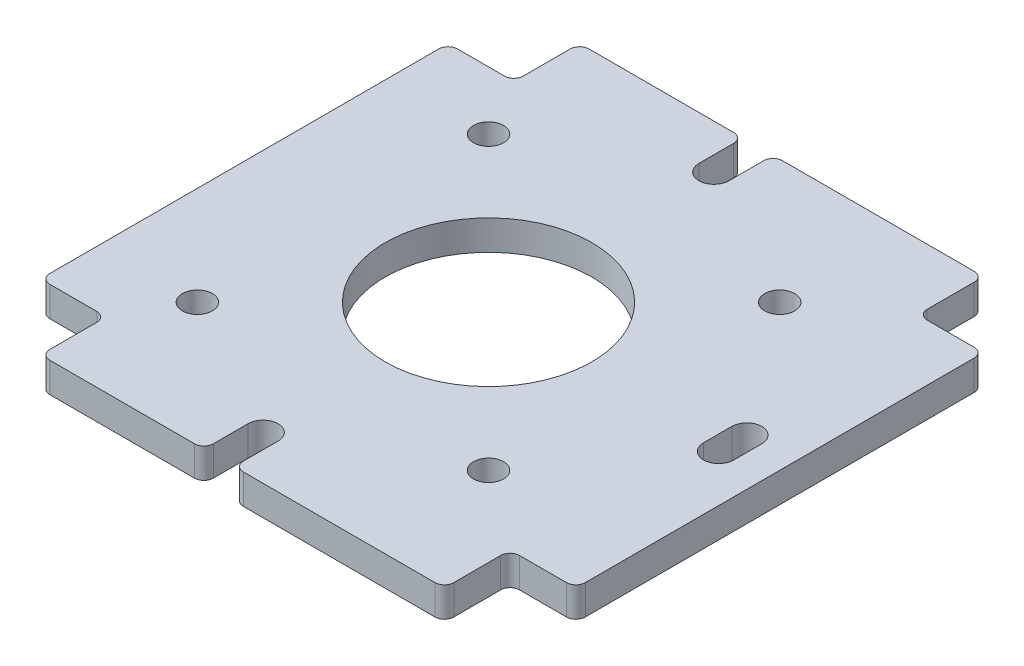
SolidWorks part; units mm, degrees
material "AISI 1045 Steel, cold drawn"
ref_plane "Front Plane" through (0, 0, 0) normal (0, 0, 1) x (1, 0, 0)
ref_plane "Top Plane" through (0, 0, 0) normal (0, 1, 0) x (1, 0, 0)
ref_plane "Right Plane" through (0, 0, 0) normal (1, 0, 0) x (0, 0, -1)
sketch "Sketch1" plane through (0, 0, 0) normal (0, 1, 0) x (1, 0, 0)
  line L1 (15.5, -15.5) -> (-15.5, -15.5) construction
  line L2 (15.5, -15.5) -> (15.5, 15.5) construction
  line L3 (15.5, 15.5) -> (-15.5, 15.5) construction
  line L4 (-15.5, -15.5) -> (-15.5, 15.5) construction
  line L5 (15.5, -15.5) -> (-15.5, 15.5) construction
  line L6 (15.5, 15.5) -> (-15.5, -15.5) construction
  line L7 (21, -21) -> (-21, -21)
  line L8 (21, -21) -> (21, 21)
  line L9 (21, 21) -> (-21, 21)
  line L10 (-21, -21) -> (-21, 21)
  line L11 (21, -21) -> (-21, 21) construction
  line L12 (21, 21) -> (-21, -21) construction
  circle A0 centre (0, 0) radius 11
  dimension "D1" = 22
  dimension "D2" = 31
  dimension "D3" = 42
extrude "Boss-Extrude1" add sketch "Sketch1" along normal mid plane 3.175
hole_wizard "M3 Clearance Hole1" positions "Sketch2" profile "Sketch3" hole size "M3" standard "ANSI Metric" end condition through all
sketch "Sketch2" plane through (0, 1.5875, 0) normal (0, 1, 0) x (1, 0, 0)
  point P0 (-15.5, 15.5)
  point P3 (15.5, 15.5)
  point P6 (15.5, -15.5)
  point P9 (-15.5, -15.5)
sketch "Sketch3" plane through (-15.5, 1.5875, -15.5) normal (1, 0, 0) x (0, 0, 1)
  line L0 (0, 0) -> (0, 3.175)
  line L1 (0, 3.175) -> (1.6, 3.175)
  line L2 (1.6, 3.175) -> (1.6, 0)
  line L5 (1.6, 0) -> (0, 0)
  line L11 (0, -6.35) -> (0, 107.95) construction
  dimension "Thru Hole Dia." = 3.2
  dimension "Thru Hole Depth" = 3.175
sketch "Sketch4" plane through (0, 1.5875, 0) normal (0, 1, 0) x (1, 0, 0)
  line L0 (0, -24) -> (0, -29) construction
  line L1 (1.6, -24) -> (1.6, -28.7)
  line L2 (-1.6, -24) -> (-1.6, -28.7)
  line L3 (26, 1.5) -> (26, -1.5) construction
  line L4 (27.6, 1.5) -> (27.6, -1.5)
  line L5 (24.4, 1.5) -> (24.4, -1.5)
  line L6 (-19, -21) -> (14, -21)
  line L9 (-21, -21) -> (21, -21) construction
  line L10 (-21, 21) -> (-26, 21)
  line L11 (21, -21) -> (21, 21) construction
  line L12 (21, 0) -> (-21, 0) construction
  line L13 (0, 24) -> (0, 29) construction
  line L14 (1.6, 28.7) -> (14, 28.7)
  line L15 (-19, -21) -> (-19, -28.7)
  line L16 (-19, -28.7) -> (-1.6, -28.7)
  line L17 (14, -28.7) -> (14, -21)
  line L18 (-21, 21) -> (-21, -21) construction
  line L19 (1.6, -28.7) -> (14, -28.7)
  line L20 (14, 28.7) -> (14, 21)
  line L21 (-19, 28.7) -> (-1.6, 28.7)
  line L22 (-19, 21) -> (-19, 28.7)
  line L23 (-19, 21) -> (14, 21)
  line L24 (-1.6, 24) -> (-1.6, 28.7)
  line L25 (1.6, 24) -> (1.6, 28.7)
  line L26 (21, 14) -> (31, 14)
  line L27 (31, 14) -> (31, -14)
  line L28 (31, -14) -> (21, -14)
  line L29 (21, 21) -> (-21, 21) construction
  line L30 (21, 14) -> (21, -14)
  line L31 (-26, 21) -> (-26, -21)
  line L32 (-26, -21) -> (-21, -21)
  line L33 (-21, 21) -> (-21, -21)
  arc A0 (1.6, -24) -> (-1.6, -24) centre (0, -24) ccw
  arc A2 (27.6, 1.5) -> (24.4, 1.5) centre (26, 1.5) ccw
  arc A3 (24.4, -1.5) -> (27.6, -1.5) centre (26, -1.5) ccw
  arc A6 (1.6, 24) -> (-1.6, 24) centre (0, 24) cw
  point P10 (26, 0)
  point P17 (0, 0)
  dimension "D1" = 1.6
  dimension "D12" = 1.6
  dimension "D2" = 3
  dimension "D3" = 5
  dimension "D4" = 10
  dimension "D5" = 5
  dimension "D6" = 7.7
  dimension "D7" = 7
  dimension "D8" = 7
  dimension "D9" = 7
  dimension "D10" = 7
  dimension "D11" = 3
  dimension "D13" = 5
extrude "Boss-Extrude2" add sketch "Sketch4" against normal up to vertex (3.175 mm away) up to point (21, -1.5875, -21)
sketch "Sketch5" plane through (0, 1.5875, 0) normal (0, 1, 0) x (1, 0, 0)
  line L0 (21, -14) -> (31, -14) construction
  line L17 (31, 14) -> (21, 14)
  line L18 (31, 14) -> (31, 21)
  line L19 (31, 21) -> (21, 21)
  line L20 (21, 14) -> (21, 21)
  line L21 (14, 28.7) -> (24, 28.7)
  line L22 (14, 28.7) -> (14, 21)
  line L23 (14, 21) -> (24, 21)
  line L24 (24, 28.7) -> (24, 21)
  line L25 (31, -14) -> (21, -14)
  line L26 (31, -14) -> (31, -21)
  line L27 (31, -21) -> (21, -21)
  line L28 (21, -14) -> (21, -21)
  line L29 (31, -14) -> (31, 14) construction
  line L30 (-19, -21) -> (-19, -28.7) construction
  line L31 (14, -28.7) -> (24, -28.7)
  line L32 (14, -28.7) -> (14, -21)
  line L33 (14, -21) -> (24, -21)
  line L34 (24, -28.7) -> (24, -21)
  line L35 (-26, -21) -> (-19, -21)
  line L36 (-26, -21) -> (-26, -21.7)
  line L37 (-26, -21.7) -> (-19, -21.7)
  line L38 (-19, -21) -> (-19, -21.7)
  line L39 (-19, 28.7) -> (-19, 21) construction
  line L40 (-26, 21) -> (-19, 21)
  line L41 (-26, 21) -> (-26, 21.7)
  line L42 (-26, 21.7) -> (-19, 21.7)
  line L43 (-19, 21) -> (-19, 21.7)
  line L44 (-1.6, 28.7) -> (-19, 28.7) construction
  line L45 (31, 21) -> (24, 21)
  line L46 (31, 21) -> (31, 21.7)
  line L47 (31, 21.7) -> (24, 21.7)
  line L48 (24, 21) -> (24, 21.7)
  line L49 (31, -21) -> (24, -21)
  line L50 (31, -21) -> (31, -21.7)
  line L51 (31, -21.7) -> (24, -21.7)
  line L52 (24, -21) -> (24, -21.7)
  line L53 (-19, -28.7) -> (-1.6, -28.7) construction
  line L54 (-26, 21) -> (-26, -21) construction
  line L55 (-19, 21) -> (-26, 21) construction
  circle M1 centre (-15.5, 15.5) radius 1.6
  circle M2 centre (15.5, 15.5) radius 1.6
  circle M3 centre (15.5, -15.5) radius 1.6
  circle M4 centre (-15.5, -15.5) radius 1.6
  line M6 (-26, -21) -> (-19, -21)
  line M7 (-19, -21) -> (-19, -28.7)
  line M8 (-19, -28.7) -> (-1.6, -28.7)
  line M9 (-1.6, -28.7) -> (-1.6, -24)
  arc M10 (-1.6, -24) -> (1.6, -24) centre (0, -24) cw
  line M11 (1.6, -24) -> (1.6, -28.7)
  line M12 (1.6, -28.7) -> (14, -28.7)
  line M13 (14, -28.7) -> (14, -21)
  line M14 (14, -21) -> (21, -21)
  line M15 (21, -21) -> (21, -14)
  line M16 (21, -14) -> (31, -14)
  line M17 (31, -14) -> (31, 14)
  line M18 (31, 14) -> (21, 14)
  line M19 (21, 14) -> (21, 21)
  line M20 (21, 21) -> (14, 21)
  line M21 (14, 21) -> (14, 28.7)
  line M22 (14, 28.7) -> (1.6, 28.7)
  line M23 (1.6, 28.7) -> (1.6, 24)
  arc M24 (1.6, 24) -> (-1.6, 24) centre (0, 24) cw
  line M25 (-1.6, 24) -> (-1.6, 28.7)
  line M26 (-1.6, 28.7) -> (-19, 28.7)
  line M27 (-19, 28.7) -> (-19, 21)
  line M28 (-19, 21) -> (-26, 21)
  circle M29 centre (0, 0) radius 11
  line M30 (24.4, -1.5) -> (24.4, 1.5)
  arc M31 (24.4, 1.5) -> (27.6, 1.5) centre (26, 1.5) cw
  line M32 (27.6, 1.5) -> (27.6, -1.5)
  arc M33 (27.6, -1.5) -> (24.4, -1.5) centre (26, -1.5) cw
  dimension "D1" = 7
  dimension "D2" = 7
  dimension "D3" = 7
extrude "Boss-Extrude3" add sketch "Sketch5" against normal up to surface (3.175 mm away) contours M28 M6 M7 M8 M9 M10 M11 M12 M13 M14 M15 M16 M17 M18 M19 M20 M21 M22 M23 M24 M25 M26 M27 M2 M4 M29 M33 M30 M31 M32 M3 M1 | M21 M20 | M19 M18 | L22 M16 M15 | L17 L20 M14 M13 | L36 L37 M7 M6 | L51 L50 L27 L34 | L46 L47 L24 L19 | L42 L41 M28 M27 region at (-22.5, 1.5875, -21.35) region at (26, 1.5875, -17.5) region at (-22.5, 1.5875, 21.35) region at (26, 1.5875, 17.5) region at (27.5, 1.5875, -21.35) region at (19, 1.5875, -24.85) region at (27.5, 1.5875, 21.35) region at (19, 1.5875, 24.85) up to face at (-15.5, -1.5875, -13.9)
fillet "Fillet1" radius 1 16 edges at (-1.6, 0, 28.7) (1.6, 0, 28.7) (-19, 0, 28.7) (1.6, 0, -28.7) (-1.6, 0, -28.7) (-19, 0, -28.7) (24, 0, -28.7) (24, 0, 28.7) (-26, 0, 21.7) (-19, 0, 21.7) (24, 0, 21.7) (31, 0, 21.7) (31, 0, -21.7) (24, 0, -21.7) (-19, 0, -21.7) (-26, 0, -21.7)
